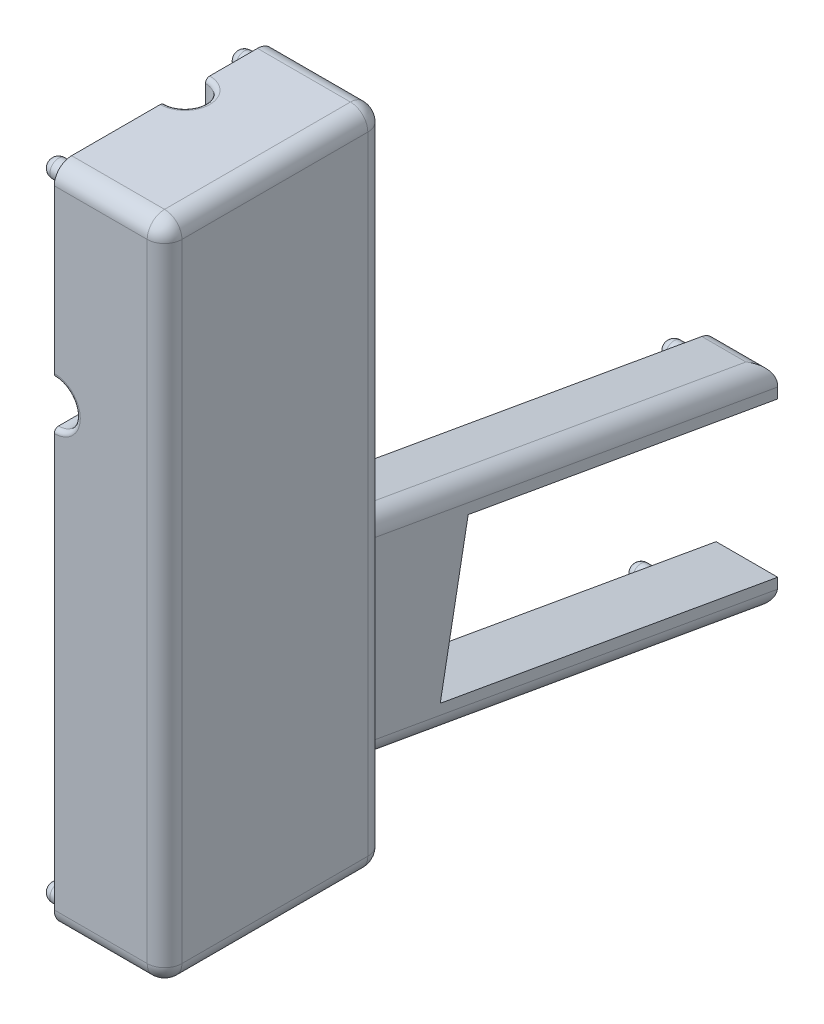
SolidWorks part; units mm, degrees
ref_plane "Front Plane" through (0, 0, 0) normal (0, 0, 1) x (1, 0, 0)
ref_plane "Top Plane" through (0, 0, 0) normal (0, 1, 0) x (1, 0, 0)
ref_plane "Right Plane" through (0, 0, 0) normal (1, 0, 0) x (0, 0, -1)
sketch "Sketch1" plane through (0, 0, 0) normal (0, 1, 0) x (1, 0, 0)
  line L1 (0, 0) -> (25.4, 0)
  line L2 (0, 0) -> (0, 50.8)
  line L3 (0, 50.8) -> (25.4, 50.8)
  line L4 (25.4, 0) -> (25.4, 50.8)
  dimension "D1" = 25.4
  dimension "D2" = 50.8
extrude "Boss-Extrude1" add sketch "Sketch1" along normal blind 152.4
sketch "Sketch2" plane through (0, 0, 0) normal (-1, 0, 0) x (0, 0, 1)
  line L0 (0, 152.4) -> (0, 0) construction
  line L1 (-6.35, 146.05) -> (-44.45, 146.05)
  line L2 (-6.35, 146.05) -> (-6.35, 6.35)
  line L3 (-6.35, 6.35) -> (-44.45, 6.35)
  line L4 (-44.45, 146.05) -> (-44.45, 6.35)
  line L5 (-50.8, 152.4) -> (0, 152.4) construction
  line L6 (-50.8, 152.4) -> (-50.8, 0) construction
  line L7 (-50.8, 0) -> (0, 0) construction
  dimension "D1" = 6.35
  dimension "D2" = 6.35
  dimension "D3" = 6.35
  dimension "D4" = 6.35
extrude "Cut-Extrude1" cut sketch "Sketch2" against normal blind 19.05
sketch "Sketch3" plane through (0, 0, 0) normal (0, 0, 1) x (1, 0, 0)
  line L0 (0, 152.4) -> (0, 0) construction
  line L1 (0, 110) -> (0, 100)
  arc A0 (0, 110) -> (0, 100) centre (0, 105) cw
  dimension "D1" = 100
extrude "HitLED" cut sketch "Sketch3" against normal up to next
sketch "Sketch5" plane through (0, 146.05, 0) normal (0, -1, 0) x (1, 0, 0)
  line L0 (0, -6.35) -> (0, -44.45) construction
  line L1 (0, -25.4) -> (0, -34.8)
  arc A0 (0, -25.4) -> (0, -34.8) centre (0, -30.1) cw
extrude "IRLED" cut sketch "Sketch5" against normal up to next
sketch "Sketch6" plane through (19.05, 0, 0) normal (-1, 0, 0) x (0, 0, 1)
  line L0 (-33.53, 146.05) -> (-33.53, 44.45)
  line L1 (-27.18, 146.05) -> (-41.45, 146.05)
  line L2 (-27.18, 146.05) -> (-27.18, 44.45)
  line L3 (-27.18, 44.45) -> (-41.45, 44.45)
  line L4 (-41.45, 146.05) -> (-41.45, 44.45)
  line L5 (-35.1, 44.45) -> (-35.1, 146.05)
  line L7 (-6.35, 146.05) -> (-44.45, 146.05) construction
  line L8 (-44.45, 146.05) -> (-44.45, 6.35) construction
  line M8 (-6.35, 146.05) -> (-44.45, 146.05)
  dimension "D1" = 0
  dimension "D2" = 3
  dimension "D3" = 1.57
  dimension "D4" = 6.35
  dimension "D5" = 6.35
  dimension "D6" = 101.6
extrude "PCB" add sketch "Sketch6" along normal blind 6.35 contours L3 L2 L0 M8 | L3 L5 L1 L4 region at (19.05, 95.25, -30.355) region at (19.05, 95.25, -38.275)
sketch "Sketch13" plane through (0, 0, -25.4) normal (-1, 0, 0) x (0, 0, 1)
  line L4 (-25.4, 61.1358) -> (-25.4, 12.7)
  line L5 (-25.4, 12.7) -> (-127, -5.2148)
  line L6 (-127, -5.2148) -> (-127, 43.221)
  line L7 (-127, 43.221) -> (-25.4, 61.1358)
  dimension "D1" = 47.7
  dimension "D2" = 12.7
extrude "Butt" add sketch "Sketch13" against normal blind 14.175
sketch "Sketch15" plane through (0, 0, 0) normal (-1, 0, 0) x (0, 0, 1)
  line L0 (-81.1356, 49.3389) -> (-74.7033, 14.9332)
  line L1 (-81.1356, 49.3389) -> (-148.1061, 37.5302)
  line L2 (-74.7033, 14.9332) -> (-141.6738, 3.1245)
  line L4 (-50.8, 61.1358) -> (-152.4, 43.221) construction
  line L6 (-148.1061, 37.5302) -> (-152.4, 36.7731)
  line L7 (-152.4, 43.221) -> (-152.4, -5.2148) construction
  line L10 (-141.6738, 3.1245) -> (-152.4, 1.2331)
  line L11 (-152.4, 1.2331) -> (-152.4, 36.7731)
  dimension "D2" = 35
  dimension "D3" = 6.35
extrude "BatteryPack" cut sketch "Sketch15" against normal up to next
fillet "Fillet-Body" radius 4 15 edges at (14.175, 3.7426, -101.6) (7.0875, -5.2148, -152.4) (7.0875, 12.7, -50.8) (14.175, 36.9179, -50.8) (7.0875, 43.221, -152.4) (14.175, 52.1784, -101.6) (7.0875, 61.1358, -50.8) (12.7, 152.4, -50.8) (12.7, 152.4, 0) (25.4, 152.4, -25.4) (25.4, 76.2, -50.8) (25.4, 76.2, 0) (25.4, 0, -25.4) (12.7, 0, -50.8) (12.7, 0, 0)
fillet "Fillet-LEDs" radius 1 2 edges at (4.7, 152.4, -30.1) (5, 105, 0)
sketch "Sketch16" plane through (0, 0, 0) normal (-1, 0, 0) x (0, 0, 1)
  line L0 (0, 148.4) -> (0, 111) construction
  line L1 (-24.4, 152.4) -> (-4, 152.4) construction
  line L3 (-46.8, 0) -> (-4, 0) construction
  line L5 (-50.8, 148.4) -> (-50.8, 64.4922) construction
  circle A0 centre (-4, 148.4) radius 2
  circle A1 centre (-4, 4) radius 2
  circle A2 centre (-46.8, 148.4) radius 2
  circle A3 centre (-46.8, 4) radius 2
  point P16 (0, 0)
  dimension "D1" = 4
  dimension "D3" = 4
  dimension "D2" = 4
  dimension "D4" = 4
extrude "PressFit" add sketch "Sketch16" along normal blind 5
fillet "Fillet-PressFit" radius 2 4 edges at (-5, 4, -44.8) (-5, 4, -2) (-5, 148.4, -44.8) (-5, 148.4, -2)
sketch "Sketch17" plane through (0, 0, 0) normal (-1, 0, 0) x (0, 0, 1)
  line L1 (-81.1356, 49.3389) -> (-152.4, 36.7731) construction
  line L6 (-152.4, 1.2331) -> (-74.7033, 14.9332) construction
  line L8 (-74.7033, 14.9332) -> (-81.1356, 49.3389) construction
  circle A0 centre (-145.735, 41.1723) radius 2
  circle A1 centre (-138.1357, 0.5243) radius 2
  point P8 (0, 0)
  dimension "D1" = 65
  dimension "D2" = 3.175
  dimension "D3" = 3.175
  dimension "D4" = 65
extrude "PressFit-Bottom" add sketch "Sketch17" along normal blind 5
fillet "Fillet-PressFit-Bottom" radius 2 2 edges at (-5, 0.5243, -136.1357) (-5, 41.1723, -143.735)
